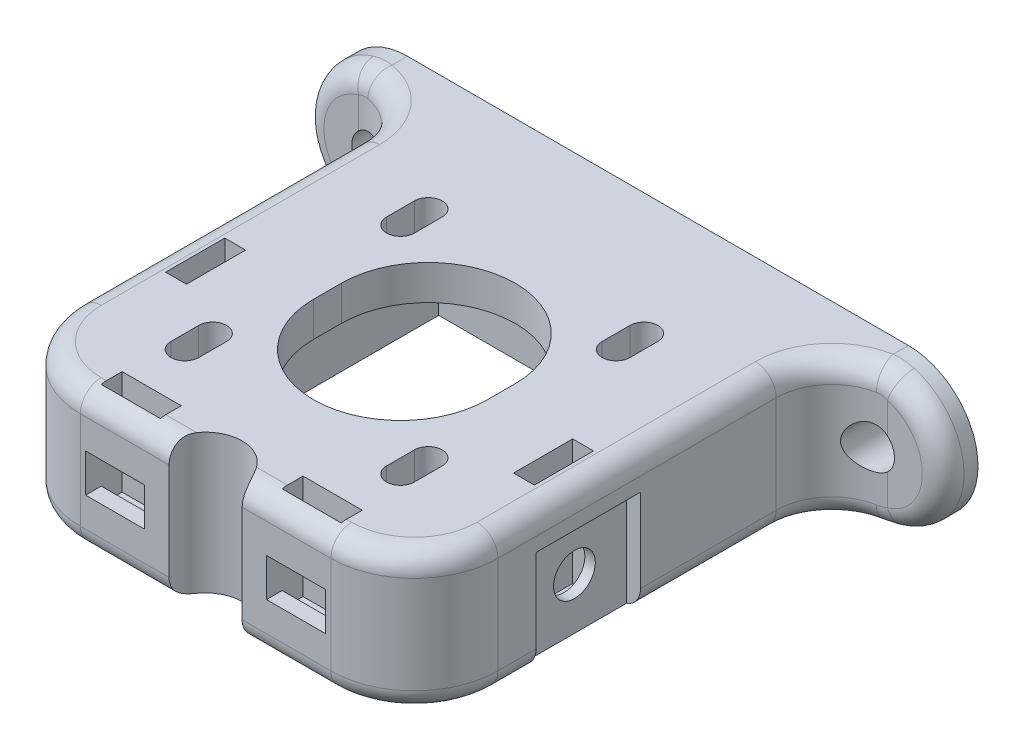
SolidWorks part; units mm, degrees
ref_plane "Front Plane" through (0, 0, 0) normal (0, 0, 1) x (1, 0, 0)
ref_plane "Top Plane" through (0, 0, 0) normal (0, 1, 0) x (1, 0, 0)
ref_plane "Right Plane" through (0, 0, 0) normal (1, 0, 0) x (0, 0, -1)
sketch "Sketch1" plane through (0, 0, 0) normal (0, 1, 0) x (1, 0, 0)
  line L0 (38, 30) -> (46, 30)
  line L2 (-30, 22) -> (-30, -18)
  line L3 (-18, -30) -> (18, -30)
  line L4 (30, 22) -> (30, -18)
  line L5 (-30, 30) -> (30, -30) construction
  line L6 (-30, -30) -> (30, 30) construction
  line L7 (-46, 35) -> (46, 35)
  line L8 (-46, 35) -> (-46, 30)
  line L9 (-46, 30) -> (-38, 30)
  line L10 (46, 35) -> (46, 30)
  arc A0 (18, -30) -> (30, -18) centre (18, -18) ccw
  arc A1 (-30, -18) -> (-18, -30) centre (-18, -18) ccw
  arc A2 (38, 30) -> (30, 22) centre (38, 22) ccw
  arc A3 (-38, 30) -> (-30, 22) centre (-38, 22) cw
  point P0 (0, 0)
  point P10 (0, 35)
  dimension "D1" = 12
  dimension "D2" = 8
  dimension "D3" = 65
  dimension "D4" = 60
  dimension "D5" = 5
  dimension "D6" = 16
extrude "Boss-Extrude1" add sketch "Sketch1" along normal blind 20
sketch "Sketch2" plane through (0, 0, 0) normal (0, -1, 0) x (1, 0, 0)
  line L0 (46, -35) -> (-46, -35) construction
  line L1 (-21.5, -25) -> (21.5, -25)
  line L2 (-21.5, -25) -> (-21.5, 19)
  line L3 (-17.5, 24) -> (17.5, 24)
  line L4 (21.5, -25) -> (21.5, 19)
  line L5 (-21.5, -25) -> (21.5, 24) construction
  line L6 (-21.5, 24) -> (21.5, -25) construction
  line L7 (-21.5, 19) -> (-17.5, 24)
  line L8 (17.5, 24) -> (21.5, 19)
  point P0 (0, -0.5)
  dimension "D1" = 49
  dimension "D2" = 43
  dimension "D3" = 10
  dimension "D4" = 5
  dimension "D5" = 4
  dimension "D6" = 4
  dimension "D7" = 5
extrude "Cut-Extrude1" cut sketch "Sketch2" against normal blind 15
sketch "Sketch3" plane through (0, 15, 0) normal (0, -1, 0) x (1, 0, 0)
  line L0 (0, 24) -> (0, -25) construction
  line L1 (17.5, 24) -> (-17.5, 24) construction
  line L2 (-21.5, -25) -> (21.5, -25) construction
  line L3 (-15.494, 17.494) -> (-15.494, 13.494) construction
  line L4 (-13.494, 17.494) -> (-13.494, 13.494)
  line L5 (-17.494, 17.494) -> (-17.494, 13.494)
  line L6 (-21.5, 0) -> (21.5, 0) construction
  line L7 (-21.5, 19) -> (-21.5, -25) construction
  line L8 (21.5, -25) -> (21.5, 19) construction
  line L9 (0, 2) -> (0, -2) construction
  line L10 (12.5, 2) -> (12.5, -2)
  line L11 (-12.5, 2) -> (-12.5, -2)
  line L12 (-15.494, -17.494) -> (-15.494, -13.494) construction
  line L13 (-13.494, -17.494) -> (-13.494, -13.494)
  line L14 (-17.494, -17.494) -> (-17.494, -13.494)
  line L15 (15.494, -17.494) -> (15.494, -13.494) construction
  line L16 (13.494, -17.494) -> (13.494, -13.494)
  line L17 (17.494, -17.494) -> (17.494, -13.494)
  line L18 (15.494, 17.494) -> (15.494, 13.494) construction
  line L19 (13.494, 17.494) -> (13.494, 13.494)
  line L20 (17.494, 17.494) -> (17.494, 13.494)
  line L21 (-21.5, -25) -> (21.5, -25) construction
  line L22 (-15.494, 15.494) -> (0, 15.494) construction
  line L23 (-15.494, 15.494) -> (-15.494, 0) construction
  arc A0 (-13.494, 17.494) -> (-17.494, 17.494) centre (-15.494, 17.494) ccw
  arc A1 (-17.494, 13.494) -> (-13.494, 13.494) centre (-15.494, 13.494) ccw
  arc A2 (12.5, 2) -> (-12.5, 2) centre (0, 2) ccw
  arc A3 (-12.5, -2) -> (12.5, -2) centre (0, -2) ccw
  arc A4 (-13.494, -17.494) -> (-17.494, -17.494) centre (-15.494, -17.494) cw
  arc A5 (-17.494, -13.494) -> (-13.494, -13.494) centre (-15.494, -13.494) cw
  arc A6 (13.494, -17.494) -> (17.494, -17.494) centre (15.494, -17.494) ccw
  arc A7 (17.494, -13.494) -> (13.494, -13.494) centre (15.494, -13.494) ccw
  arc A8 (13.494, 17.494) -> (17.494, 17.494) centre (15.494, 17.494) cw
  arc A9 (17.494, 13.494) -> (13.494, 13.494) centre (15.494, 13.494) cw
  point P8 (-15.494, 15.494)
  point P21 (0, 0)
  point P28 (-15.494, -15.494)
  point P35 (15.494, -15.494)
  point P42 (15.494, 15.494)
  dimension "D1" = 4
  dimension "D2" = 25
  dimension "D3" = 4
  dimension "D4" = 4
  dimension "D5" = 25
  dimension "D6" = 0.994
extrude "Cut-Extrude2" cut sketch "Sketch3" against normal through all
sketch "Sketch4" plane through (0, 20, 0) normal (0, 1, 0) x (1, 0, 0)
  line L0 (0, 35) -> (0, -30) construction
  line L1 (46, 35) -> (-46, 35) construction
  line L2 (-18, -30) -> (18, -30) construction
  line L3 (-25, -5) -> (-30, -5) construction
  line L4 (-26.5, -0.75) -> (-23.5, -0.75)
  line L5 (-26.5, -0.75) -> (-26.5, -9.25)
  line L6 (-26.5, -9.25) -> (-23.5, -9.25)
  line L7 (-23.5, -0.75) -> (-23.5, -9.25)
  line L8 (-26.5, -0.75) -> (-23.5, -9.25) construction
  line L9 (-26.5, -9.25) -> (-23.5, -0.75) construction
  line L16 (-30, 22) -> (-30, -18) construction
  line L25 (26.5, -9.25) -> (23.5, -0.75) construction
  line L26 (26.5, -0.75) -> (23.5, -9.25) construction
  line L27 (25, -5) -> (30, -5) construction
  line L28 (23.5, -0.75) -> (23.5, -9.25)
  line L29 (26.5, -9.25) -> (23.5, -9.25)
  line L30 (26.5, -0.75) -> (26.5, -9.25)
  line L31 (26.5, -0.75) -> (23.5, -0.75)
  point P6 (-25, -5)
  dimension "D1" = 3
  dimension "D2" = 8.5
  dimension "D5" = 3.5
  dimension "D6" = 40
extrude "Cut-Extrude3" cut sketch "Sketch4" against normal blind 18
sketch "Sketch8" plane through (0, 20, 0) normal (0, 1, 0) x (1, 0, 0)
  line L0 (0, 34.1419) -> (0, -30) construction
  line L1 (-17.25, -27.75) -> (-8.75, -27.75)
  line L2 (-17.25, -27.75) -> (-17.25, -24.75)
  line L3 (-17.25, -24.75) -> (-8.75, -24.75)
  line L4 (-8.75, -27.75) -> (-8.75, -24.75)
  line L5 (-17.25, -27.75) -> (-8.75, -24.75) construction
  line L6 (-17.25, -24.75) -> (-8.75, -27.75) construction
  line L7 (-13, -26.25) -> (-13, -35.2361) construction
  line L8 (13, -26.25) -> (13, -35.2361) construction
  line L9 (17.25, -24.75) -> (8.75, -27.75) construction
  line L10 (17.25, -27.75) -> (8.75, -24.75) construction
  line L11 (8.75, -27.75) -> (8.75, -24.75)
  line L12 (17.25, -24.75) -> (8.75, -24.75)
  line L13 (17.25, -27.75) -> (17.25, -24.75)
  line L14 (17.25, -27.75) -> (8.75, -27.75)
  line L15 (-18, -30) -> (18, -30) construction
  point P2 (-13, -26.25)
  point P17 (0, -30)
  dimension "D1" = 3
  dimension "D2" = 8.5
  dimension "D3" = 13
  dimension "D4" = 3.75
extrude "Cut-Extrude7" cut sketch "Sketch8" against normal blind 15
sketch "Sketch5" plane through (0, 2, 0) normal (0, 1, 0) x (1, 0, 0)
  line L0 (0, 35) -> (0, -30) construction
  line L1 (46, 35) -> (-46, 35) construction
  line L2 (-18, -30) -> (18, -30) construction
  line L3 (-23.5, -9.25) -> (-23.5, -0.75) construction
  line L4 (-23.5, -0.75) -> (-26.5, -0.75) construction
  line L8 (-8.75, -24.75) -> (-17.25, -24.75) construction
  line L9 (-17.25, -24.75) -> (-17.25, -27.75) construction
  circle A0 centre (-25, -5) radius 1.5
  circle A1 centre (-13, -26.25) radius 1.5
  circle A2 centre (13, -26.25) radius 1.5
  circle A3 centre (25, -5) radius 1.5
  point P12 (-23.5, -5)
  point P15 (-25, -0.75)
  point P18 (-13, -24.75)
  point P21 (-17.25, -26.25)
  dimension "D1" = 3
extrude "Cut-Extrude4" cut sketch "Sketch5" against normal through all
sketch "Sketch6" plane through (0, 20, 0) normal (0, 1, 0) x (1, 0, 0)
  line L0 (-18, -30) -> (18, -30) construction
  line L1 (-5.25, -30) -> (5.25, -30)
  arc A0 (-5.25, -30) -> (5.25, -30) centre (0, -30) cw
  dimension "D1" = 10.5
extrude "Cut-Extrude5" cut sketch "Sketch6" against normal through all
sketch "Sketch7" plane through (0, 0, 30) normal (0, 0, 1) x (1, 0, 0)
  line L0 (0, 0) -> (0, 20) construction
  line L1 (-17.25, 12.75) -> (-8.75, 12.75)
  line L2 (-17.25, 12.75) -> (-17.25, 7.25)
  line L3 (-17.25, 7.25) -> (-8.75, 7.25)
  line L4 (-8.75, 12.75) -> (-8.75, 7.25)
  line L5 (-17.25, 12.75) -> (-8.75, 7.25) construction
  line L6 (-17.25, 7.25) -> (-8.75, 12.75) construction
  line L7 (17.25, 7.25) -> (8.75, 12.75) construction
  line L8 (17.25, 12.75) -> (8.75, 7.25) construction
  line L9 (8.75, 12.75) -> (8.75, 7.25)
  line L10 (17.25, 7.25) -> (8.75, 7.25)
  line L11 (17.25, 12.75) -> (17.25, 7.25)
  line L12 (17.25, 12.75) -> (8.75, 12.75)
  line L13 (-5.25, 0) -> (-5.25, 20) construction
  point P0 (-13, 10)
  point P12 (13, 10)
  point P15 (-5.25, 10)
  dimension "D1" = 5.5
extrude "Cut-Extrude6" cut sketch "Sketch7" against normal up to next
sketch "Sketch9" plane through (0, 0, 0) normal (0, -1, 0) x (1, 0, 0)
  line L0 (0, -35) -> (0, 30) construction
  line L1 (46, -35) -> (-46, -35) construction
  line L2 (-30, -22) -> (-30, 18) construction
  line L3 (-30, 12.5) -> (-28, 12.5)
  line L4 (-30, 12.5) -> (-30, -2.5)
  line L5 (-30, -2.5) -> (-28, -2.5)
  line L6 (-28, 12.5) -> (-28, -2.5)
  line L7 (28, 12.5) -> (28, -2.5)
  line L8 (30, -2.5) -> (28, -2.5)
  line L9 (30, 12.5) -> (30, -2.5)
  line L10 (30, 12.5) -> (28, 12.5)
  point P11 (-28, 5)
  dimension "D1" = 15
  dimension "D2" = 2
extrude "Cut-Extrude8" cut sketch "Sketch9" against normal offset from surface (15 mm away) 5 up to face at (13, 20, 26.25)
sketch "Sketch10" plane through (-28, 0, 0) normal (-1, 0, 0) x (0, 0, 1)
  line L0 (-2.5, 15) -> (12.5, 15) construction
  line L1 (-2.5, 15) -> (-2.5, 0) construction
  circle A0 centre (5, 7.5) radius 3
  point P4 (5, 15)
  point P7 (-2.5, 7.5)
  dimension "D1" = 6
extrude "Cut-Extrude9" cut sketch "Sketch10" against normal through all
sketch "Sketch11" plane through (0, 0, -35) normal (0, 0, -1) x (-1, 0, 0)
  line L0 (0, 20) -> (0, 0) construction
  line L1 (-46, 20) -> (46, 20) construction
  line L2 (-46, 0) -> (46, 0) construction
  line L3 (-46, 20) -> (-46, 0) construction
  line L4 (-36, 20) -> (36, 20)
  line L5 (36, 0) -> (-36, 0)
  arc A0 (-36, 20) -> (-36, 0) centre (-36, 10) ccw
  arc A1 (36, 20) -> (36, 0) centre (36, 10) cw
extrude "Cut-Extrude10" cut sketch "Sketch11" against normal through all flip side to cut
sketch "Sketch12" plane through (0, 0, -35) normal (0, 0, -1) x (-1, 0, 0)
  circle A0 centre (-36, 10) radius 3
  circle A1 centre (36, 10) radius 3
  arc A2 (-36, 20) -> (-36, 0) centre (-36, 10) ccw construction
  arc A3 (36, 0) -> (36, 20) centre (36, 10) ccw construction
  dimension "D1" = 6
extrude "Cut-Extrude11" cut sketch "Sketch12" against normal through all
fillet "Fillet1" radius 3 22 edges at (26.4853, 0, 26.4853) (30, 0, -12.25) (31.6754, 0, -26.899) (46, 10, -30) (31.6754, 20, -26.899) (30, 20, -2) (26.4853, 20, 26.4853) (-11.625, 0, 30) (-30, 0, -12.25) (-31.6754, 0, -26.899) (-46, 10, -30) (-31.6754, 20, -26.899) (-30, 20, -2) (-11.625, 20, 30) (11.625, 0, 30) (11.625, 20, 30) (-26.4853, 0, 26.4853) (-26.4853, 20, 26.4853)
